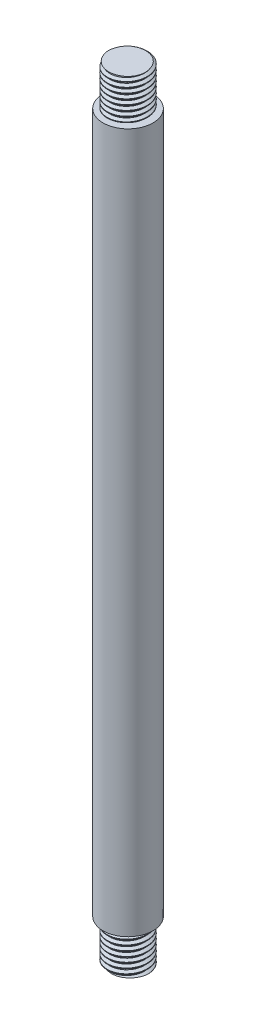
SolidWorks part; units mm, degrees
ref_plane "Front Plane" through (0, 0, 0) normal (0, 0, 1) x (1, 0, 0)
ref_plane "Top Plane" through (0, 0, 0) normal (0, 1, 0) x (1, 0, 0)
ref_plane "Right Plane" through (0, 0, 0) normal (1, 0, 0) x (0, 0, -1)
sketch "Sketch1" plane through (0, 0, 0) normal (0, 0, 1) x (1, 0, 0)
  line L0 (0, 0) -> (0, 156) construction
  line L1 (0, 156) -> (4, 156)
  line L2 (4, 156) -> (4, 148)
  line L3 (4, 148) -> (5, 148)
  line L4 (5, 148) -> (5, 8)
  line L5 (5, 8) -> (4, 8)
  line L6 (4, 8) -> (4, 0)
  line L7 (4, 0) -> (0, 0)
  line L8 (0, 0) -> (0, 156)
  dimension "D1" = 156
  dimension "D2" = 10
  dimension "D3" = 8
  dimension "D4" = 4
  dimension "D5" = 8
  dimension "D6" = 8
revolve "Revolve1" add sketch "Sketch1" angle 360 about L0
thread "Thread1" pitch 1 method cut trim with start face yes trim with end face yes profile "Thread Profile1" start angle 0, offset 2, length 10, pitch 1, diameter 8
ref_plane "Plane1" through (-4, 158, 0) normal (0, 0, 1) x (-1, 0, 0)
sketch "Thread Profile1" plane through (-4, 158, 0) normal (0, 0, 1) x (-1, 0, 0)
  line L0 (0, 0) -> (0, 1) construction
  line L11 (0, 0) -> (0, 0.875)
  line L12 (0, 0.875) -> (-0.5413, 0.5625)
  line L13 (-0.5413, 0.5625) -> (-0.5413, 0.3125)
  line L15 (-0.5413, 0.3125) -> (0, 0)
  line L17 (-0.5413, 0.4375) -> (0, 0.4375) construction
  point P2 (0, 0)
  dimension "Pitch" = 1
  dimension "Profile_Angle" = 60
  dimension "Profile_Land" = 0.25
  dimension "Profile_Height" = 0.5413
thread "Thread2" pitch 1 method cut trim with start face yes trim with end face yes profile "Thread Profile2" start angle 0, offset 2, length 10, pitch 1, diameter 8
ref_plane "Plane3" through (4, -2, 0) normal (0, 0, 1) x (1, 0, 0)
sketch "Thread Profile2" plane through (4, -2, 0) normal (0, 0, 1) x (1, 0, 0)
  line L0 (0, 0) -> (0, 1) construction
  line L11 (0, 0) -> (0, 0.875)
  line L12 (0, 0.875) -> (-0.5413, 0.5625)
  line L13 (-0.5413, 0.5625) -> (-0.5413, 0.3125)
  line L15 (-0.5413, 0.3125) -> (0, 0)
  line L17 (-0.5413, 0.4375) -> (0, 0.4375) construction
  point P2 (0, 0)
  dimension "Pitch" = 1
  dimension "Profile_Angle" = 60
  dimension "Profile_Land" = 0.25
  dimension "Profile_Height" = 0.5413
